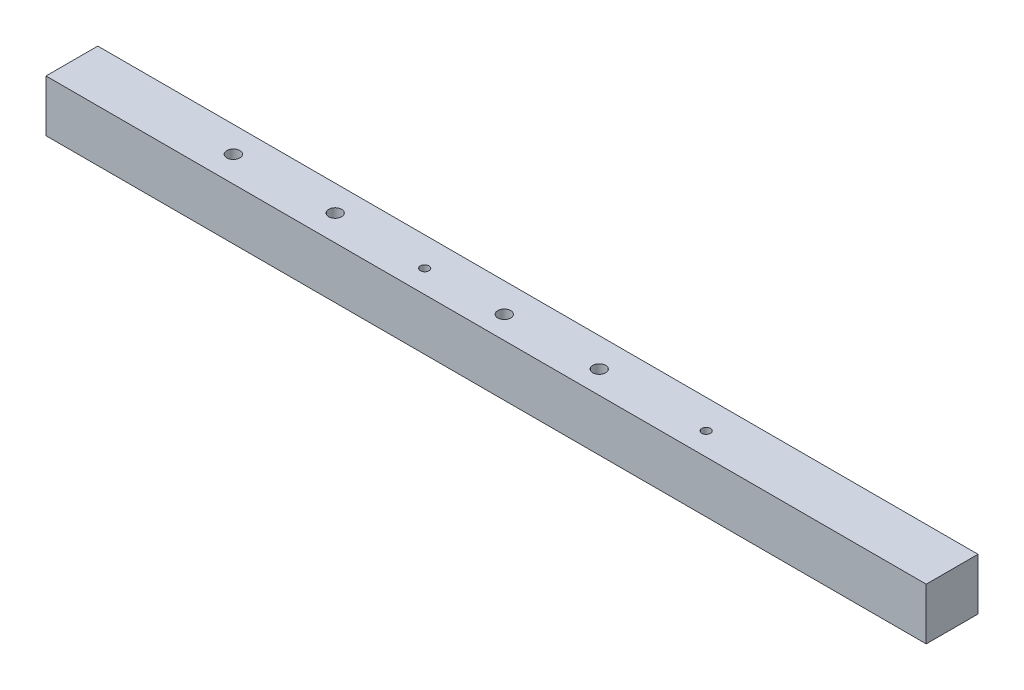
SolidWorks part; units mm, degrees
ref_plane "Front Plane" through (0, 0, 0) normal (0, 0, 1) x (1, 0, 0)
ref_plane "Top Plane" through (0, 0, 0) normal (0, 1, 0) x (1, 0, 0)
ref_plane "Right Plane" through (0, 0, 0) normal (1, 0, 0) x (0, 0, -1)
sketch "Sketch1" plane through (0, 0, 0) normal (0, 1, 0) x (1, 0, 0)
  line L1 (0, 0) -> (647.7, 0)
  line L2 (0, 0) -> (0, 38.1)
  line L3 (0, 38.1) -> (647.7, 38.1)
  line L4 (647.7, 0) -> (647.7, 38.1)
  circle A0 centre (118.8022, 19.05) radius 4.7625
  circle A1 centre (193.7322, 19.05) radius 4.7625
  circle A2 centre (320.4706, 16.7416) radius 4.7625
  circle A3 centre (390.3206, 16.7416) radius 4.7625
  circle A4 centre (261.9041, 16.7416) radius 3.175
  circle A5 centre (469.0411, 16.7416) radius 3.175
  point P15 (0, 19.05)
  point P18 (261.9041, 16.7416)
  dimension "D3" = 9.525
  dimension "D5" = 9.525
  dimension "D6" = 126.7384
  dimension "D7" = 69.85
  dimension "D8" = 9.525
  dimension "D9" = 9.525
  dimension "D11" = 6.35
  dimension "D12" = 6.35
  dimension "D1" = 38.1
  dimension "D2" = 647.7
  dimension "D4" = 74.93
  dimension "D10" = 207.137
extrude "Boss-Extrude1" add sketch "Sketch1" along normal blind 38.1
